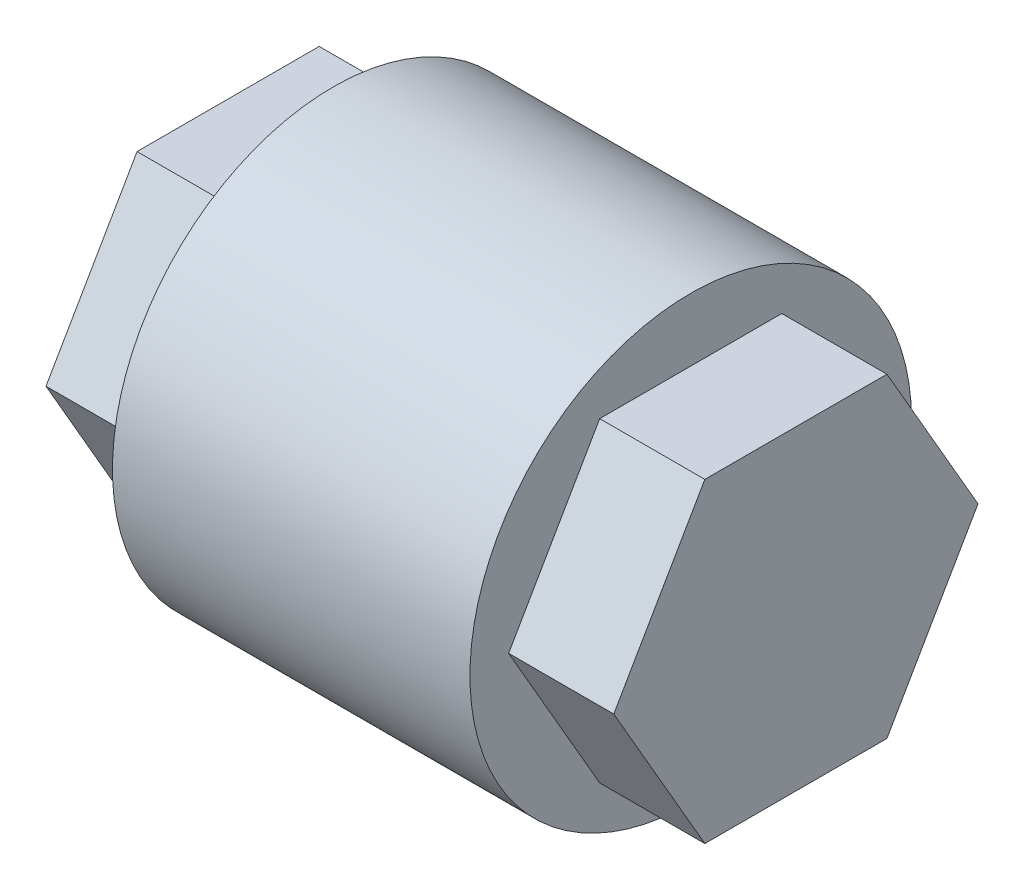
SolidWorks part; units mm, degrees
ref_plane "Плоскость1" through (0, 0, 0) normal (0, 0, 1) x (1, 0, 0)
ref_plane "Плоскость2" through (0, 0, 0) normal (0, 1, 0) x (1, 0, 0)
ref_plane "Плоскость3" through (0, 0, 0) normal (1, 0, 0) x (0, 0, -1)
sketch "Эскиз1" plane through (0, 0, 0) normal (1, 0, 0) x (0, 0, -1)
  line L1 (17.3205, 0) -> (8.6603, 15)
  line L2 (8.6603, 15) -> (-8.6603, 15)
  line L3 (-8.6603, 15) -> (-17.3205, 0)
  line L4 (-17.3205, 0) -> (-8.6603, -15)
  line L5 (-8.6603, -15) -> (8.6603, -15)
  line L6 (8.6603, -15) -> (17.3205, 0)
  circle A0 centre (0, 0) radius 15 construction
  dimension "D1" = 30
extrude "Основание-Вытянуть" add sketch "Эскиз1" along normal blind 10
sketch "Эскиз2" plane through (10, 0, 0) normal (1, 0, 0) x (0, 0, -1)
  circle A0 centre (0, 0) radius 21
  dimension "D1" = 42
extrude "Бобышка-Вытянуть1" add sketch "Эскиз2" along normal blind 34
sketch "Эскиз3" plane through (44, 0, 0) normal (1, 0, 0) x (0, 0, -1)
  line L1 (17.3205, 0) -> (8.6603, 15)
  line L2 (8.6603, 15) -> (-8.6603, 15)
  line L3 (-8.6603, 15) -> (-17.3205, 0)
  line L4 (-17.3205, 0) -> (-8.6603, -15)
  line L5 (-8.6603, -15) -> (8.6603, -15)
  line L6 (8.6603, -15) -> (17.3205, 0)
  line L7 (8.6603, 15) -> (-8.6603, 15) construction
  line L8 (-8.6603, 15) -> (-17.3205, 0) construction
  line L9 (8.6603, -15) -> (17.3205, 0) construction
extrude "Бобышка-Вытянуть2" add sketch "Эскиз3" along normal blind 10
ref_axis "Ось1" through (78.3987, 0, 0) along (-1, 0, 0)
